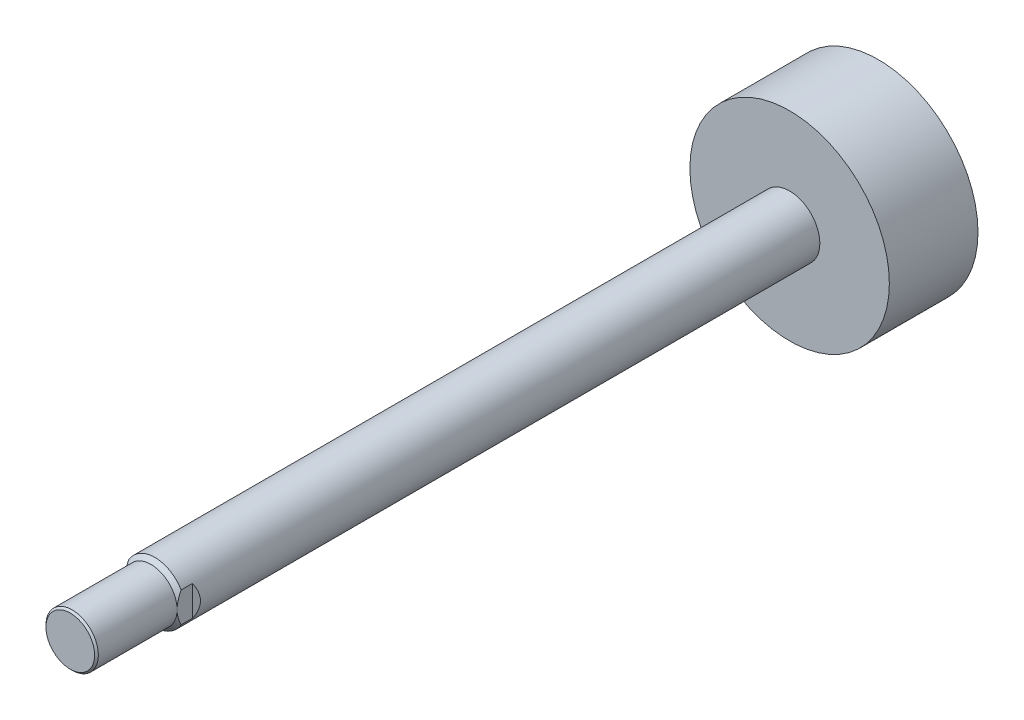
SolidWorks part; units mm, degrees
material "A3钢"
ref_plane "前视基准面" through (0, 0, 0) normal (0, 0, 1) x (1, 0, 0)
ref_plane "上视基准面" through (0, 0, 0) normal (0, 1, 0) x (1, 0, 0)
ref_plane "右视基准面" through (0, 0, 0) normal (1, 0, 0) x (0, 0, -1)
sketch "草图1" plane through (0, 0, 0) normal (1, 0, 0) x (0, 0, -1)
  line L0 (-52, 0) -> (-52, 12.08)
  line L1 (-52, 12.08) -> (-51.08, 13)
  line L2 (-51.08, 13) -> (-12, 13)
  line L3 (-12, 13) -> (-10, 15)
  line L4 (-10, 15) -> (305, 15)
  line L5 (305, 15) -> (305, 49.5)
  line L6 (305, 49.5) -> (349, 49.5)
  line L7 (349, 49.5) -> (349, 0)
  line L8 (349, 0) -> (-52, 0)
  line L9 (349, 0) -> (-52, 0) construction
revolve "旋转1" add sketch "草图1" angle 360 about L9 reverse direction yes
cosmetic thread "装饰螺纹线1" parameters "D1"=36, "D2"=24.16
sketch "草图2" plane through (0, 0, 0) normal (0, 1, 0) x (1, 0, 0)
  line L0 (13, -4.4) -> (13, -12)
  line L1 (13, -12) -> (15, -12)
  line L2 (15, -12) -> (15, -2.4)
  line L3 (15, -2.4) -> (13, -4.4)
extrude "切除-拉伸1" cut sketch "草图2" along normal blind 15 and the other way blind 15
sketch "草图3" plane through (0, 0, 0) normal (0, 1, 0) x (1, 0, 0)
  line L0 (-15, -2.4) -> (-15, -12)
  line L1 (-15, -12) -> (-13, -12)
  line L2 (-13, -12) -> (-13, -4.4)
  line L3 (-13, -4.4) -> (-15, -2.4)
extrude "切除-拉伸2" cut sketch "草图3" along normal blind 15 and the other way blind 15
ref_plane "基准面1" through (0, 0, -20) normal (0, 0, 1) x (1, 0, 0)
ref_plane "基准面2" through (0, 0, 32) normal (0, 0, 1) x (1, 0, 0)
ref_plane "基准面3" through (0, 0, -686) normal (0, 0, 1) x (1, 0, 0)
ref_plane "基准面4" through (0, 0, -624.5) normal (0, 0, 1) x (1, 0, 0)
ref_plane "基准面5" through (0, 0, -631.25) normal (0, 0, 1) x (1, 0, 0)
ref_plane "IP1_POLE XY" through (0, 0, -20) normal (0, 0, -1) x (-1, 0, 0)
ref_plane "IP1_POLE XZ" through (0, 0, 0) normal (0, 1, 0) x (1, 0, 0)
ref_plane "IP1_POLE YZ" through (0, 0, 0) normal (1, 0, 0) x (0, 0, -1)
ref_axis "IP1_POLE X" through (-80.9, 0, -20) along (1, 0, 0)
ref_axis "IP1_POLE Y" through (0, 50, -20) along (0, -1, 0)
ref_axis "IP1_POLE Z" through (0, 0, -80.9) along (0, 0, 1)
sketch3d "IP1_POLE"
  point P0 (0, 0, -20)
ref_plane "IP_A_NUT XY" through (0, 0, -624.5) normal (0, 0, -1) x (-1, 0, 0)
ref_plane "IP_A_NUT XZ" through (0, 0, 0) normal (0, 1, 0) x (1, 0, 0)
ref_plane "IP_A_NUT YZ" through (0, 0, 0) normal (1, 0, 0) x (0, 0, -1)
ref_axis "IP_A_NUT X" through (-80.9, 0, -624.5) along (1, 0, 0)
ref_axis "IP_A_NUT Y" through (0, 50, -624.5) along (0, -1, 0)
ref_axis "IP_A_NUT Z" through (0, 0, -80.9) along (0, 0, 1)
sketch3d "IP_A_NUT"
  point P0 (0, 0, -624.5)
ref_plane "IP_NUT XY" through (0, 0, 32) normal (0, 0, 1) x (1, 0, 0)
ref_plane "IP_NUT XZ" through (0, 0, 0) normal (0, -1, 0) x (-1, 0, 0)
ref_plane "IP_NUT YZ" through (0, 0, 0) normal (1, 0, 0) x (0, 0, -1)
ref_axis "IP_NUT X" through (-80.9, 0, 32) along (1, 0, 0)
ref_axis "IP_NUT Y" through (0, -50, 32) along (0, 1, 0)
ref_axis "IP_NUT Z" through (0, 0, 80.9) along (0, 0, -1)
sketch3d "IP_NUT"
  point P0 (0, 0, 32)
ref_plane "IP_NUT_2 XY" through (0, 0, -686) normal (0, 0, -1) x (-1, 0, 0)
ref_plane "IP_NUT_2 XZ" through (0, 0, 0) normal (0, 1, 0) x (1, 0, 0)
ref_plane "IP_NUT_2 YZ" through (0, 0, 0) normal (1, 0, 0) x (0, 0, -1)
ref_axis "IP_NUT_2 X" through (-80.9, 0, -686) along (1, 0, 0)
ref_axis "IP_NUT_2 Y" through (0, 50, -686) along (0, -1, 0)
ref_axis "IP_NUT_2 Z" through (0, 0, -80.9) along (0, 0, 1)
sketch3d "IP_NUT_2"
  point P0 (0, 0, -686)
ref_plane "IP_NUT_A_2 XY" through (0, 0, -631.25) normal (0, 0, -1) x (-1, 0, 0)
ref_plane "IP_NUT_A_2 XZ" through (0, 0, 0) normal (0, 1, 0) x (1, 0, 0)
ref_plane "IP_NUT_A_2 YZ" through (0, 0, 0) normal (1, 0, 0) x (0, 0, -1)
ref_axis "IP_NUT_A_2 X" through (-80.9, 0, -631.25) along (1, 0, 0)
ref_axis "IP_NUT_A_2 Y" through (0, 50, -631.25) along (0, -1, 0)
ref_axis "IP_NUT_A_2 Z" through (0, 0, -80.9) along (0, 0, 1)
sketch3d "IP_NUT_A_2"
  point P0 (0, 0, -631.25)
